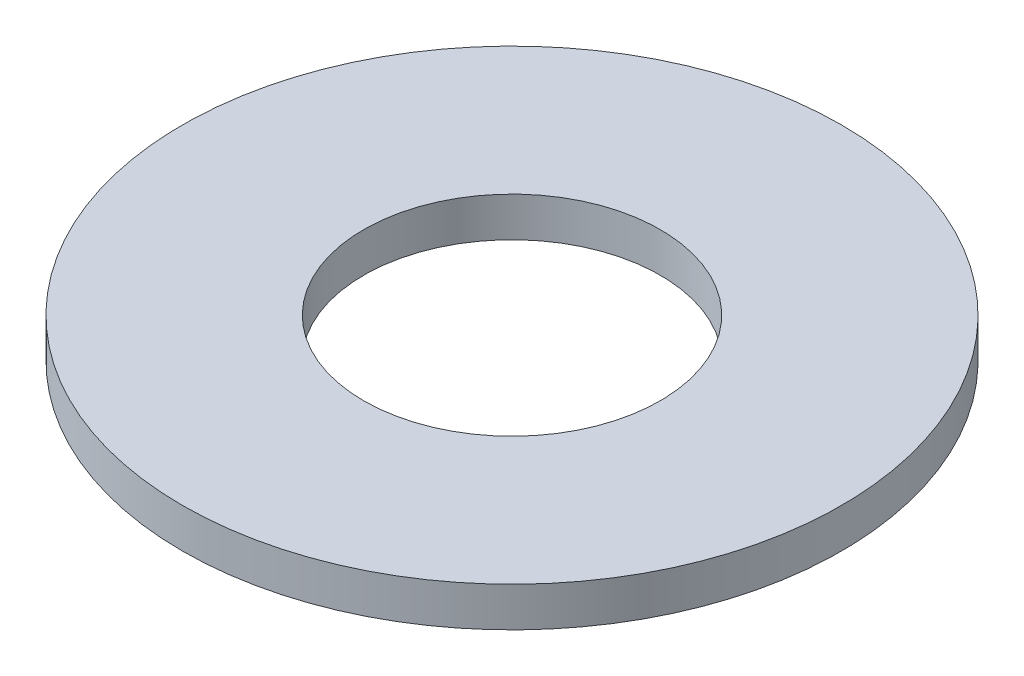
SolidWorks part; units mm, degrees
ref_plane "Front Plane" through (0, 0, 0) normal (0, 0, 1) x (1, 0, 0)
ref_plane "Top Plane" through (0, 0, 0) normal (0, 1, 0) x (1, 0, 0)
ref_plane "Right Plane" through (0, 0, 0) normal (1, 0, 0) x (0, 0, -1)
sketch "Sketch1" plane through (0, 0, 0) normal (0, 1, 0) x (1, 0, 0)
  circle A0 centre (0, 0) radius 50
  dimension "FLANGE_OD" = 100
extrude "Boss-Extrude1" add sketch "Sketch1" along normal blind 6
sketch "Sketch2" plane through (0, 0, 0) normal (0, 1, 0) x (1, 0, 0)
  circle A0 centre (0, 0) radius 22.5
  dimension "BORE_D" = 45
extrude "Cut-Extrude1" cut sketch "Sketch2" along normal through all
sketch "Sketch3" plane through (0, 6, 0) normal (0, 1, 0) x (1, 0, 0)
  circle A0 centre (0, 0) radius 14.4585 construction
  circle A1 centre (-14.4585, 0) radius 4.6321
  dimension "BOLT_D" = 9.2641
  dimension "BOLT_PCD" = 28.917
extrude "Cut-Extrude2" cut sketch "Sketch3" against normal blind 5.3828 rebuild error yes
pattern_circular "CirPattern1" count 3 over 360 rebuild error yes
